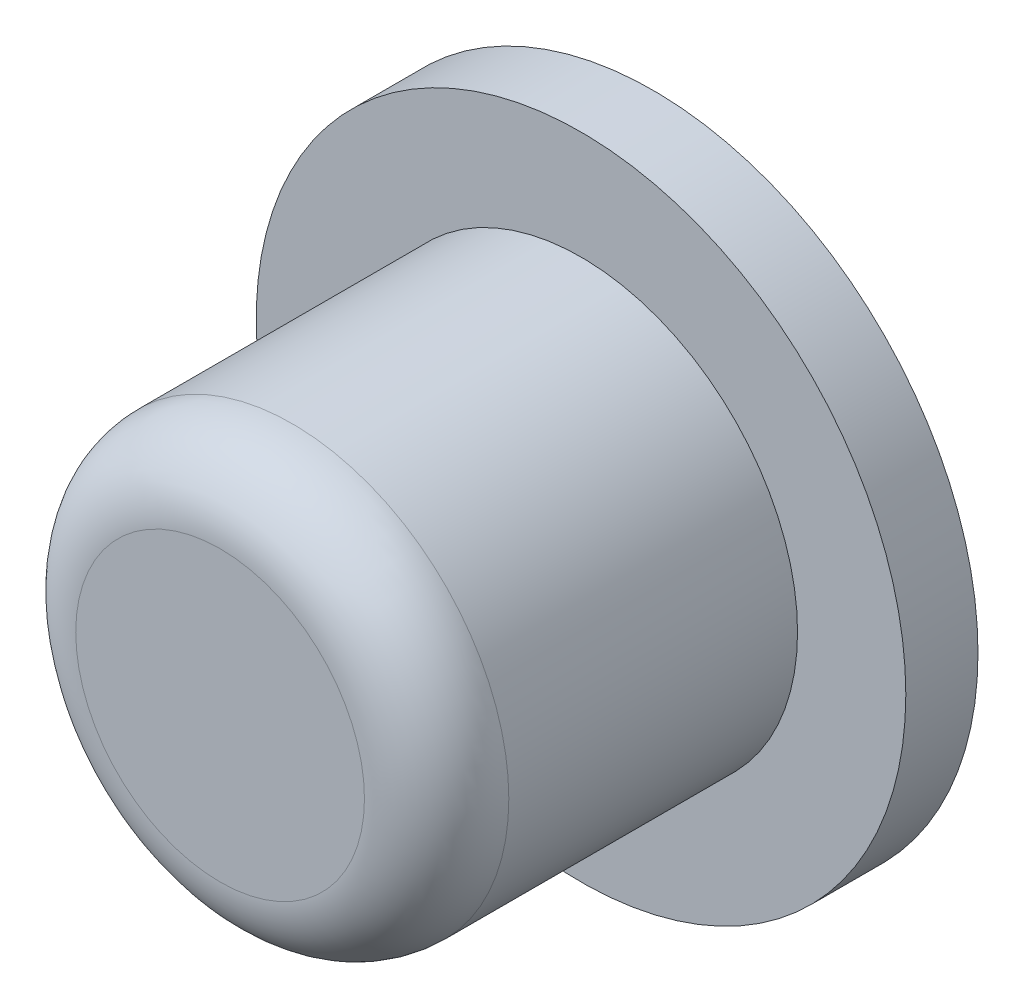
SolidWorks part; units mm, degrees
ref_plane "前视基准面" through (0, 0, 0) normal (0, 0, 1) x (1, 0, 0)
ref_plane "上视基准面" through (0, 0, 0) normal (0, 1, 0) x (1, 0, 0)
ref_plane "右视基准面" through (0, 0, 0) normal (1, 0, 0) x (0, 0, -1)
other "Configuration Table"
sketch "草图1" plane through (0, 0, 0) normal (0, 0, 1) x (1, 0, 0)
  circle A0 centre (0, 0) radius 1.9
  circle A1 centre (0, 0) radius 3
  circle A2 centre (0, 0) radius 4.5
  point P7 (0, 0)
  dimension "D4" = 3.8
  dimension "D1" = 6
  dimension "D2" = 1.5
extrude "凸台-拉伸1" add sketch "草图1" along normal blind 6 contours A1
extrude "切除-拉伸1" cut sketch "草图1<4>" along normal blind 1.5 contours A0
sketch "草图1<4>" plane through (0, 0, 0) normal (0, 0, 1) x (1, 0, 0) same geometry as "草图1"
extrude "凸台-拉伸2" add sketch "草图1<5>" along normal blind 1 contours A2 | A1
sketch "草图1<5>" plane through (0, 0, 0) normal (0, 0, 1) x (1, 0, 0) same geometry as "草图1"
fillet "圆角1" radius 1 1 edges at (3, 0, 6)
